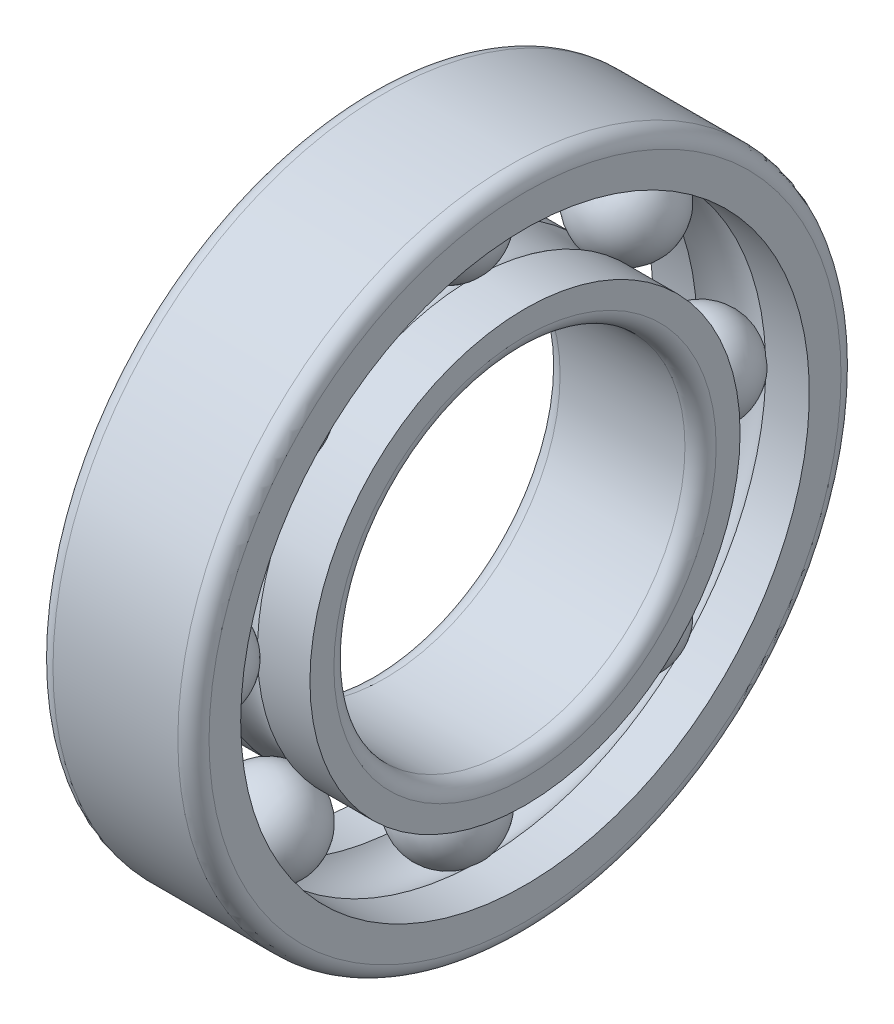
SolidWorks part; units mm, degrees
ref_plane "Face" through (0, 0, 0) normal (0, 0, 1) x (1, 0, 0)
ref_plane "Dessus" through (0, 0, 0) normal (0, 1, 0) x (1, 0, 0)
ref_plane "Droite" through (0, 0, 0) normal (1, 0, 0) x (0, 0, -1)
ref_axis "Axe" through (-2.2, 0, 0) along (1, 0, 0)
sketch "Esquisse1" plane through (0, 0, 0) normal (0, 0, 1) x (1, 0, 0)
  line L1 (0, 4.5) -> (0, -4.5) construction
  line L2 (2, 5.5138) -> (0.6542, 5.5138)
  line L3 (-2, 4.9) -> (-2, 5.5138)
  line L4 (0, 8.5) -> (0, -8.5) construction
  line L5 (2, 5.5138) -> (2, 4.9)
  line L6 (1.6, 4.5) -> (-1.6, 4.5)
  line L7 (0, 5.3166) -> (2, 5.3166) construction
  line L8 (-2, 5.5138) -> (-0.6542, 5.5138)
  line L9 (5, 0) -> (-5, 0) construction
  arc A0 (-0.6542, 5.5138) -> (0.6542, 5.5138) centre (0, 6.5) ccw
  arc A1 (-1.6, 4.5) -> (-2, 4.9) centre (-1.6, 4.9) cw
  arc A2 (2, 4.9) -> (1.6, 4.5) centre (1.6, 4.9) cw
  dimension "D bille" = 2.3669
  dimension "Rayon" = 0.4
  dimension "Diamètre int" = 9
  dimension "Diamètre ext" = 17
  dimension "Epaisseur" = 4
  dimension "D3" = 0.3945
  dimension "D1" = 6.5
revolve "Bague int" add sketch "Esquisse1" angle 360 about L9
sketch "Esquisse3" plane through (0, 0, 0) normal (0, 0, 1) x (1, 0, 0)
  line L2 (-6.7492, 6.5) -> (6.7492, 6.5) construction
  line L3 (-1.2084, 6.5) -> (1.2084, 6.5)
  arc A0 (-1.2084, 6.5) -> (1.2084, 6.5) centre (0, 6.5) ccw
  dimension "D1" = 2.4169
revolve "Bille" add sketch "Esquisse3" angle 360 about L2
sketch "Esquisse2" plane through (0, 0, 0) normal (0, 0, 1) x (1, 0, 0)
  line L0 (-1.6, 8.5) -> (1.6, 8.5)
  line L3 (-5, 7.6834) -> (0, 7.6834) construction
  line L5 (-2, 7.289) -> (-0.8821, 7.289)
  line L6 (0, 8.5) -> (0, -8.5) construction
  line L7 (2, 7.289) -> (2, 8.1)
  line L8 (-2, 7.289) -> (-2, 8.1)
  line L9 (0.8821, 7.289) -> (2, 7.289)
  line L10 (-5, 0) -> (5, 0) construction
  line L12 (-2, 4.9) -> (-2, 5.5138) construction
  arc A0 (0.8821, 7.289) -> (-0.8821, 7.289) centre (0, 6.5) ccw
  arc A1 (-0.6542, 5.5138) -> (0.6542, 5.5138) centre (0, 6.5) ccw construction
  arc A3 (-2, 8.1) -> (-1.6, 8.5) centre (-1.6, 8.1) cw
  arc A4 (2, 8.1) -> (1.6, 8.5) centre (1.6, 8.1) ccw
  point P20 (-2, 8.5)
  point P23 (2, 8.5)
  dimension "Rayon" = 0.4
  dimension "D3" = 0.3945
revolve "Bague ext" add sketch "Esquisse2" angle 360 about L10
pattern_circular "Nbr de billes" count 8 over 360 about axis through (-2.2, 0, 0) along (1, 0, 0) of "Bille"
equation "\"D bille@Esquisse1\" = \"Epaisseur@Esquisse1\"/1.69"
equation "\"D3@Esquisse1\" = \"D bille@Esquisse1\"/6"
equation "\"D1@Esquisse1\" = ((\"Diamètre ext@Esquisse1\"-\"Diamètre int@Esquisse1\")/4)+(\"Diamètre int@Esquisse1\"/2)"
equation "\"D1@Esquisse3\" = \"D bille@Esquisse1\"+0.05"
equation "\"D3@Esquisse2\" = \"D3@Esquisse1\""
